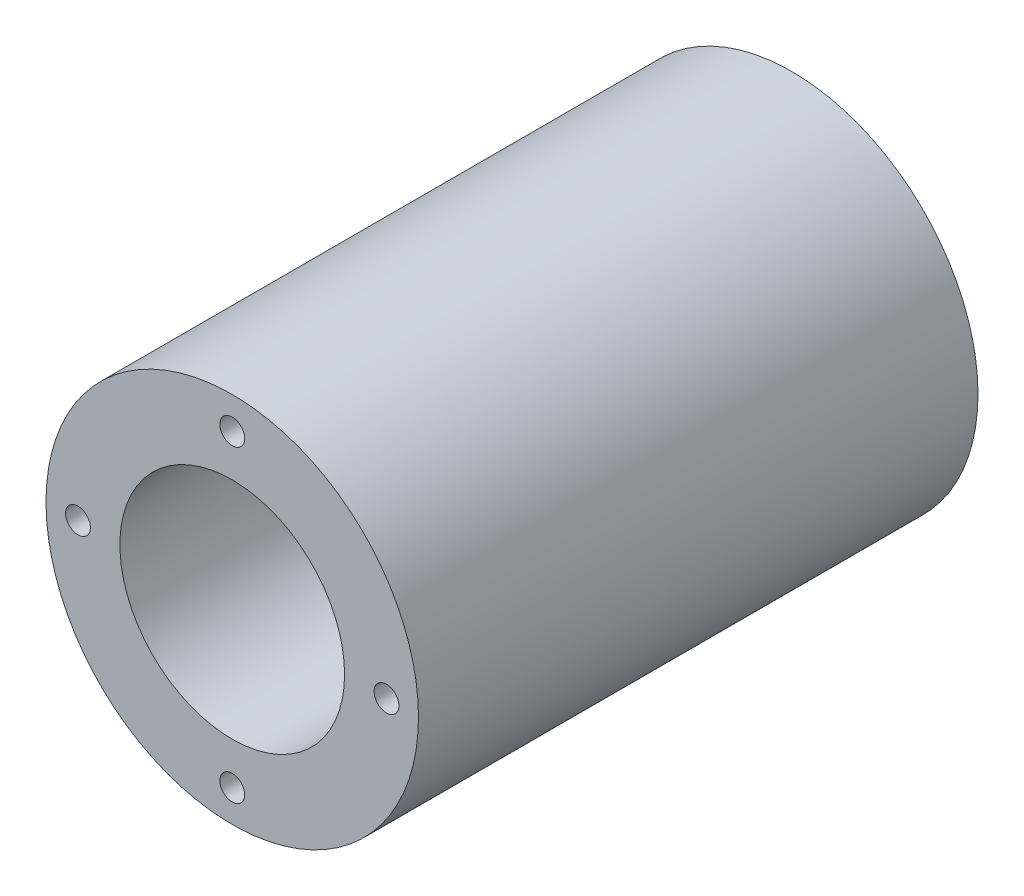
SolidWorks part; units mm, degrees
material "6061-T6 (SS)"
ref_plane "Front Plane" through (0, 0, 0) normal (0, 0, 1) x (1, 0, 0)
ref_plane "Top Plane" through (0, 0, 0) normal (0, 1, 0) x (1, 0, 0)
ref_plane "Right Plane" through (0, 0, 0) normal (1, 0, 0) x (0, 0, -1)
sketch "Sketch Spindle Skeleton" plane through (0, 0, 0) normal (1, 0, 0) x (0, 0, -1)
  line L0 (-108, -9.5) -> (-149, -9.5)
  line L5 (-1000, 0) -> (49000, 0)
  line L6 (0, -9.5) -> (0, 9.5)
  line L13 (0, 9.5) -> (-46.4, 9.5)
  line L26 (-46.4, 9.5) -> (-46.4, 14)
  line L27 (-46.4, 14) -> (-108, 14)
  line L32 (-108, 14) -> (-108, 9.5)
  line L34 (-165, 7) -> (-165, -7)
  line L36 (-108, -9.5) -> (-108, -14)
  line L37 (-108, -14) -> (-46.4, -14)
  line L38 (-46.4, -14) -> (-46.4, -9.5)
  line L39 (0, -9.5) -> (-46.4, -9.5)
  line L40 (-22.625, 37.5) -> (-14.625, 37.5)
  line L41 (-124.6, 22.6187) -> (-108, 22.6187)
  line L42 (-124.6, 22.6187) -> (-124.6, -22.6187)
  line L43 (-124.6, -22.6187) -> (-108, -22.6187)
  line L44 (-108, 22.6187) -> (-108, -22.6187)
  line L45 (-124.6, 22.6187) -> (-108, -22.6187) construction
  line L46 (-124.6, -22.6187) -> (-108, 22.6187) construction
  line L47 (-29.8, 22.6187) -> (-46.4, 22.6187)
  line L48 (-29.8, 22.6187) -> (-29.8, -22.6187)
  line L49 (-29.8, -22.6187) -> (-46.4, -22.6187)
  line L50 (-46.4, 22.6187) -> (-46.4, -22.6187)
  line L51 (-29.8, 22.6187) -> (-46.4, -22.6187) construction
  line L52 (-29.8, -22.6187) -> (-46.4, 22.6187) construction
  line L59 (-14.625, 37.5) -> (-14.625, -37.5)
  line L60 (-14.625, -37.5) -> (-22.625, -37.5)
  line L61 (-22.625, -22.6187) -> (-26.625, -22.6187)
  line L62 (-26.625, -22.6187) -> (-26.625, -12.5)
  line L63 (-26.625, -12.5) -> (-22.625, -12.5)
  line L64 (-22.625, -12.5) -> (-22.625, 12.5)
  line L65 (-22.625, 12.5) -> (-26.625, 12.5)
  line L66 (-26.625, 12.5) -> (-26.625, 22.6187)
  line L67 (-26.625, 22.6187) -> (-22.625, 22.6187)
  line L68 (-22.625, 22.6187) -> (-22.625, 37.5)
  line L69 (-22.625, -22.6187) -> (-22.625, -37.5)
  line L71 (-136.284, 37.5) -> (-23.625, 37.5)
  line L72 (-136.284, 37.5) -> (-136.284, -37.5)
  line L73 (-136.284, -37.5) -> (-23.625, -37.5)
  line L74 (-23.625, 37.5) -> (-23.625, -37.5)
  line L75 (-136.284, 37.5) -> (-23.625, -37.5) construction
  line L76 (-136.284, -37.5) -> (-23.625, 37.5) construction
  line L77 (-149, -9.5) -> (-149, -7)
  line L78 (-149, -7) -> (-165, -7)
  line L79 (-108, 9.5) -> (-149, 9.5)
  line L80 (-149, 7) -> (-165, 7)
  line L81 (-149, 9.5) -> (-149, 7)
  line L82 (-128.5, 9.5) -> (-128.5, -9.5) construction
  line L83 (-23.2, 9.5) -> (-23.2, -9.5) construction
  line L96 (-136.284, 37.5) -> (-144.284, 37.5)
  line L98 (-136.284, -37.5) -> (-144.284, -37.5)
  line L99 (-144.284, 37.5) -> (-144.284, -37.5)
  line L110 (-136.284, 37.5) -> (-136.284, -37.5)
  point P3 (0, 0)
  point P18 (-116.3, 0)
  point P24 (-38.1, 0)
  point P29 (-79.9545, 0)
  point P48 (-14.625, 31.0593)
  point P70 (-144.284, 31.0593)
sketch "Sketch1" plane through (0, 0, 0) normal (1, 0, 0) x (0, 0, -1)
  line L0 (-23.625, 37.5) -> (-23.625, -37.5) construction
  line L1 (-136.284, -37.5) -> (-23.625, -37.5) construction
  line L2 (-136.284, 37.5) -> (-136.284, -37.5) construction
  line L3 (-136.284, 37.5) -> (-23.625, 37.5) construction
  line L4 (-23.625, 37.5) -> (-23.625, -37.5)
  line L5 (-136.284, -37.5) -> (-23.625, -37.5)
  line L6 (-136.284, 37.5) -> (-136.284, -37.5)
  line L7 (-136.284, 37.5) -> (-23.625, 37.5)
  line L8 (-26.625, 22.6187) -> (-22.625, 22.6187) construction
  line L10 (-136.284, 22.6187) -> (-23.625, 22.6187)
  line L15 (-136.284, 0) -> (-23.625, 0) construction
revolve "Revolve1" add sketch "Sketch1" angle 360 about L15 region at (0, 30.0593, 79.9545)
sketch "Back Hole Top Location" plane through (0, 0, 23.625) normal (0, 0, -1) x (-1, 0, 0)
  point P1 (0, 0)
  point P2 (0, 0)
  point P9 (0, 31.0593)
hole_wizard "M6x1.0 Tapped Hole3" positions "Sketch8" profile "Sketch9" tap size "M6x1.0" standard "ANSI Metric"
sketch "Sketch8" plane through (0, 0, 23.625) normal (0, 0, -1) x (-1, 0, 0)
  point P0 (0, 31.0593)
sketch "Sketch9" plane through (0, 31.0593, 23.625) normal (1, 0, 0) x (0, 1, 0)
  line L0 (0, 0) -> (0, 16.5022)
  line L1 (0, 16.5022) -> (2.5, 15)
  line L2 (2.5, 15) -> (2.5, 0)
  line L5 (2.5, 0) -> (0, 0)
  line L10 (0, 16.5022) -> (-2.5, 15) construction
  line L11 (0, -6.35) -> (0, 107.95) construction
  dimension "Tap Drill Dia." = 5
  dimension "Tap Drill Depth" = 15
  dimension "Drill Angle" = 118
pattern_circular "BackFacePattern" count 6 over 360 about axis through (0, 0, 1000) along (0, 0, -1) of "M6x1.0 Tapped Hole3"
ref_plane "Midplane" through (0, 0, 79.9545) normal (0, 0, -1) x (-1, 0, 0)
sketch "Front Hole Top Location" plane through (0, 0, 136.284) normal (0, 0, 1) x (1, 0, 0)
  point P0 (0, 31.0593)
hole_wizard "M6x1.0 Tapped Hole2" positions "Sketch5" profile "Sketch6" tap size "M6x1.0" standard "ANSI Metric"
sketch "Sketch5" plane through (0, 0, 136.284) normal (0, 0, 1) x (1, 0, 0)
  point P0 (0, 31.0593)
sketch "Sketch6" plane through (0, 31.0593, 136.284) normal (1, 0, 0) x (0, -1, 0)
  line L0 (0, 0) -> (0, 16.5022)
  line L1 (0, 16.5022) -> (2.5, 15)
  line L2 (2.5, 15) -> (2.5, 0)
  line L5 (2.5, 0) -> (0, 0)
  line L10 (0, 16.5022) -> (-2.5, 15) construction
  line L11 (0, -6.35) -> (0, 107.95) construction
  dimension "Tap Drill Dia." = 5
  dimension "Tap Drill Depth" = 15
  dimension "Drill Angle" = 118
pattern_circular "FrontFacePattern" count 4 over 360 about axis through (0, 0, 1000) along (0, 0, -1) of "M6x1.0 Tapped Hole2"
sketch "Sketch7" plane through (0, 0, 23.625) normal (0, 0, -1) x (-1, 0, 0)
  circle A0 centre (0, 0) radius 26.9875
  circle A1 centre (0, 0) radius 25.4
  dimension "D1" = 53.975
  dimension "D2" = 50.8
extrude "Cut-Extrude1" cut sketch "Sketch7" against normal blind 0.5
